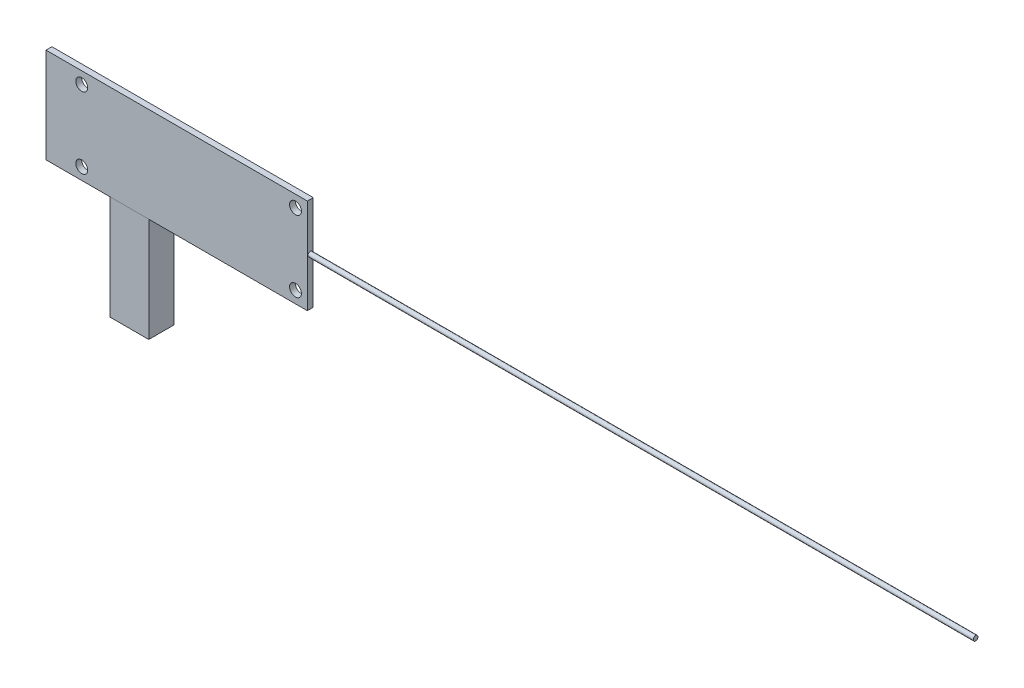
SolidWorks part; units mm, degrees
material "Printed Circuit Board"
ref_plane "Front Plane" through (0, 0, 0) normal (0, 0, 1) x (1, 0, 0)
ref_plane "Top Plane" through (0, 0, 0) normal (0, 1, 0) x (1, 0, 0)
ref_plane "Right Plane" through (0, 0, 0) normal (1, 0, 0) x (0, 0, -1)
sketch "Sketch1" plane through (0, 0, 0) normal (0, 0, 1) x (1, 0, 0)
  line L1 (-34.925, -12.7) -> (34.925, -12.7)
  line L2 (-34.925, -12.7) -> (-34.925, 12.7)
  line L3 (-34.925, 12.7) -> (34.925, 12.7)
  line L4 (34.925, -12.7) -> (34.925, 12.7)
  line L5 (-34.925, -12.7) -> (34.925, 12.7) construction
  line L6 (-34.925, 12.7) -> (34.925, -12.7) construction
  point P0 (0, 0)
  dimension "D1" = 69.85
  dimension "D2" = 25.4
extrude "Extrude1" add sketch "Sketch1" along normal blind 1.5748
sketch "Sketch2" plane through (0, 0, 1.5748) normal (0, 0, 1) x (1, 0, 0)
  line L0 (-34.925, 9.525) -> (-25.3822, 9.525) construction
  line L1 (-34.925, 12.7) -> (-34.925, -12.7) construction
  line L2 (-25.3822, 9.525) -> (31.75, 9.525) construction
  dimension "D1" = 9.5428
  dimension "D2" = 66.675
  dimension "D3" = 3.175
hole_wizard "1/8 (0.125) Diameter Hole1" positions "3DSketch1" profile "Sketch3" hole size "1/8" standard "Ansi Inch"
sketch3d "3DSketch1"
  point P0 (-25.3822, 9.525, 1.5748)
  point P3 (31.75, 9.525, 1.5748)
sketch "Sketch3" plane through (-25.3822, 9.525, 1.5748) normal (1, 0, 0) x (0, -1, 0)
  line L0 (0, 0) -> (0, 16.9559)
  line L1 (0, 16.9559) -> (1.5875, 16.002)
  line L2 (1.5875, 16.002) -> (1.5875, 0)
  line L5 (1.5875, 0) -> (0, 0)
  line L10 (0, 16.9559) -> (-1.5875, 16.002) construction
  line L11 (0, -6.35) -> (0, 107.95) construction
  dimension "Hole Dia." = 3.175
  dimension "Hole Depth" = 16.002
  dimension "Drill Angle" = 118
mirror "Mirror1" about plane through (0, 0, 0) normal (0, 1, 0) of "1/8 (0.125) Diameter Hole1"
sketch "Sketch4" plane through (34.925, 0, 0) normal (1, 0, 0) x (0, 0, -1)
  line L0 (0, 0) -> (-1.5441, 0) construction
  line L1 (0, -12.7) -> (0, 12.7) construction
  circle A0 centre (-0.772, 0) radius 0.635
  dimension "D1" = 1.27
extrude "Boss-Extrude1" add sketch "Sketch4" along normal blind 177.8
sketch "Sketch5" plane through (0, 0, 0) normal (0, 0, -1) x (-1, 0, 0)
  line L0 (34.925, -12.7) -> (-34.925, -12.7) construction
  line L1 (17.1361, -12.7) -> (9.0081, -12.7)
  line L2 (17.1361, -12.7) -> (17.1361, -3.9624)
  line L3 (17.1361, -3.9624) -> (9.0081, -3.9624)
  line L4 (9.0081, -12.7) -> (9.0081, -3.9624)
  dimension "D1" = 8.7376
  dimension "D2" = 8.128
extrude "USB Connector" add sketch "Sketch5" along normal blind 4.1402
sketch "Sketch6" plane through (0, -12.7, 0) normal (0, -1, 0) x (1, 0, 0)
  line L1 (-17.9544, 1.4835) -> (-7.548, 1.4835)
  line L2 (-17.9544, 1.4835) -> (-17.9544, -5.2984)
  line L3 (-17.9544, -5.2984) -> (-7.548, -5.2984)
  line L4 (-7.548, 1.4835) -> (-7.548, -5.2984)
  line L5 (-17.9544, 1.4835) -> (-7.548, -5.2984) construction
  line L6 (-17.9544, -5.2984) -> (-7.548, 1.4835) construction
  point P0 (-12.7512, -1.9075)
extrude "Charger" add sketch "Sketch6" along normal blind 27.94
